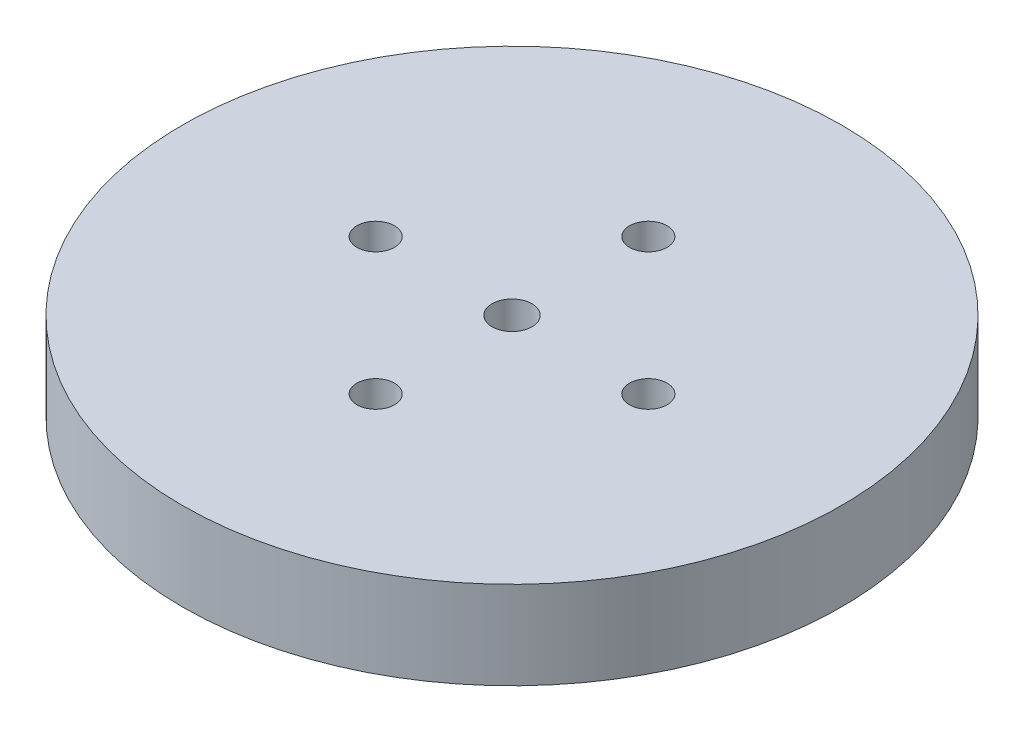
SolidWorks part; units mm, degrees
ref_plane "Front Plane" through (0, 0, 0) normal (0, 0, 1) x (1, 0, 0)
ref_plane "Top Plane" through (0, 0, 0) normal (0, 1, 0) x (1, 0, 0)
ref_plane "Right Plane" through (0, 0, 0) normal (1, 0, 0) x (0, 0, -1)
sketch "Sketch1" plane through (0, 0, 0) normal (0, 1, 0) x (1, 0, 0)
  circle A0 centre (0, 0) radius 82.5
  dimension "FLANGE_OD" = 165
extrude "Boss-Extrude1" add sketch "Sketch1" along normal blind 22
sketch "Sketch2" plane through (0, 0, 0) normal (0, 1, 0) x (1, 0, 0)
  circle A0 centre (0, 0) radius 5
  dimension "BORE_D" = 10
extrude "Cut-Extrude1" cut sketch "Sketch2" along normal through all
sketch "Sketch3" plane through (0, 22, 0) normal (0, 1, 0) x (1, 0, 0)
  circle A0 centre (0, 0) radius 34.1249 construction
  circle A1 centre (-34.1249, 0) radius 4.7046
  dimension "BOLT_D" = 9.4093
  dimension "BOLT_PCD" = 68.2497
extrude "Cut-Extrude2" cut sketch "Sketch3" against normal blind 20.825
pattern_circular "CirPattern1" count 4 over 360 about axis through (0, 0, 0) along (0, 1, 0) of "Cut-Extrude2"
